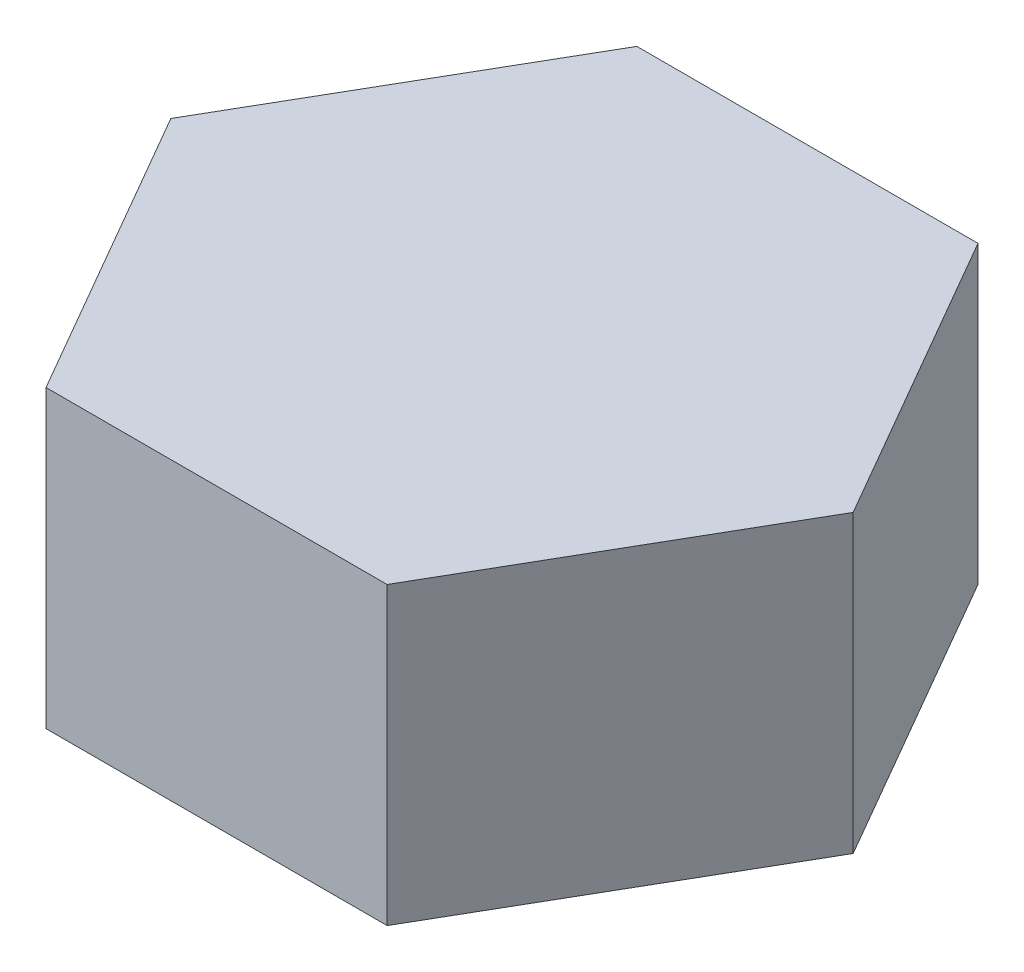
SolidWorks part; units mm, degrees
ref_plane "Front Plane" through (0, 0, 0) normal (0, 0, 1) x (1, 0, 0)
ref_plane "Top Plane" through (0, 0, 0) normal (0, 1, 0) x (1, 0, 0)
ref_plane "Right Plane" through (0, 0, 0) normal (1, 0, 0) x (0, 0, -1)
sketch "Sketch1" plane through (0, 0, 0) normal (0, 1, 0) x (1, 0, 0)
  line L0 (-5.7735, -10) -> (5.7735, -10)
  line L1 (5.7735, -10) -> (11.547, 0)
  line L2 (11.547, 0) -> (5.7735, 10)
  line L3 (5.7735, 10) -> (-5.7735, 10)
  line L4 (-5.7735, 10) -> (-11.547, 0)
  line L5 (-11.547, 0) -> (-5.7735, -10)
  line L6 (-5.7735, 10) -> (5.7735, -10) construction
  line L7 (-5.7735, -10) -> (5.7735, 10) construction
  line L8 (-11.547, 0) -> (11.547, 0) construction
  circle A0 centre (0, 0) radius 10 construction
  dimension "D1" = 20
extrude "Boss-Extrude1" add sketch "Sketch1" along normal blind 3 and the other way blind 7
ref_axis "Axis1" through (0, 5.5, 0) along (0, -1, 0)
